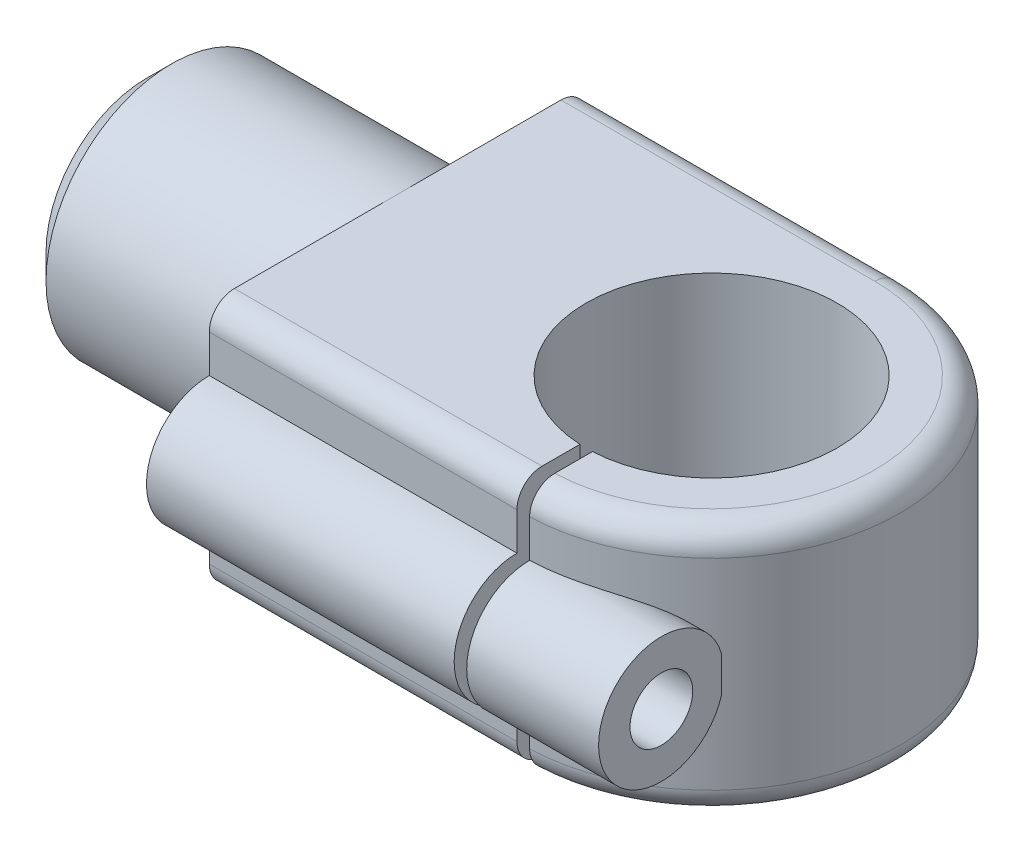
SolidWorks part; units mm, degrees
ref_plane "Front Plane" through (0, 0, 0) normal (0, 0, 1) x (1, 0, 0)
ref_plane "Top Plane" through (0, 0, 0) normal (0, 1, 0) x (1, 0, 0)
ref_plane "Right Plane" through (0, 0, 0) normal (1, 0, 0) x (0, 0, -1)
sketch "Sketch1" plane through (0, 0, 0) normal (0, 1, 0) x (1, 0, 0)
  line L0 (0, 15) -> (-30, 15)
  line L1 (-30, 15) -> (-30, -15)
  line L2 (-30, -15) -> (-0.5, -15)
  line L4 (0.5, -15) -> (0.5, -9.9875)
  line L5 (-0.5, -15) -> (-0.5, -9.9875)
  arc A0 (0.5, -9.9875) -> (-0.5, -9.9875) centre (0, 0) ccw
  arc A1 (0.5, -14.9917) -> (0, 15) centre (0, 0) ccw
  dimension "D1" = 20
  dimension "D2" = 30
  dimension "D3" = 30
extrude "Boss-Extrude1" add sketch "Sketch1" along normal blind 20 contours L4 A1 L0 L1 L2 L5 A0 region at (-12.0415, 0, -0.0669)
sketch "Sketch2" plane through (-30, 0, 0) normal (-1, 0, 0) x (0, 0, 1)
  line L0 (15, 20) -> (15, 0) construction
  circle A0 centre (15, 10) radius 5
  dimension "D1" = 10
extrude "Boss-Extrude2" add sketch "Sketch2" against normal blind 41
sketch "Sketch3" plane through (0, 20, 0) normal (0, 1, 0) x (1, 0, 0)
  line L0 (-0.5, -15) -> (-0.5, -9.9875) construction
  line L1 (0.5, -14.9917) -> (0.5, -9.9875) construction
  line L2 (-0.5, -15) -> (-0.5, -9.9875)
  line L3 (0.5, -14.9917) -> (0.5, -9.9875)
  line L4 (-0.5, -9.9875) -> (0.5, -9.9875)
  line L6 (-0.5, -15) -> (-0.5, -20)
  line L7 (-30, -20) -> (11, -20) construction
  line L8 (-0.5, -20) -> (0.5, -20)
  line L9 (0.5, -20) -> (0.5, -14.9917)
extrude "Cut-Extrude1" cut sketch "Sketch3" against normal blind 41
sketch "Sketch4" plane through (11, 0, 0) normal (1, 0, 0) x (0, 0, -1)
  circle A0 centre (-15, 10) radius 2.5
  dimension "D1" = 5
extrude "Cut-Extrude2" cut sketch "Sketch4" against normal blind 31
fillet "Fillet1" radius 2 6 edges at (-15, 0, -15) (-15, 20, -15) (-15.25, 20, 15) (-15.25, 0, 15) (14.9979, 0, -0.25) (14.9979, 20, -0.25)
sketch "Sketch5" plane through (-30, 0, 0) normal (-1, 0, 0) x (0, 0, 1)
  circle A0 centre (0, 10) radius 10
  dimension "D1" = 20
extrude "Boss-Extrude3" add sketch "Sketch5" along normal blind 15
sketch "Sketch6" plane through (-30, 0, 0) normal (-1, 0, 0) x (0, 0, 1)
  line L3 (0, 20) -> (-13, 20)
  line L4 (0, 0) -> (13, 0)
  line L5 (15, 2) -> (15, 5)
  line L6 (15, 15) -> (15, 18)
  line L7 (13, 20) -> (0, 20)
  line L8 (0, 0) -> (13, 0)
  line L9 (15, 2) -> (15, 5)
  line L10 (15, 15) -> (15, 18)
  line L11 (13, 20) -> (0, 20)
  line L12 (-15, 18) -> (-15, 2)
  line L13 (-13, 0) -> (0, 0)
  line L14 (0, 20) -> (-13, 20)
  line L15 (-15, 18) -> (-15, 2)
  line L16 (-13, 0) -> (0, 0)
  arc A3 (0, 20) -> (0, 0) centre (0, 10) ccw
  arc A4 (0, 0) -> (0, 20) centre (0, 10) ccw
  arc A5 (13, 0) -> (15, 2) centre (13, 2) ccw
  arc A6 (15, 5) -> (15, 15) centre (15, 10) ccw
  arc A7 (15, 18) -> (13, 20) centre (13, 18) ccw
  arc A8 (0, 0) -> (0, 20) centre (0, 10) ccw
  arc A9 (13, 0) -> (15, 2) centre (13, 2) ccw
  arc A10 (15, 5) -> (15, 15) centre (15, 10) ccw
  arc A11 (15, 18) -> (13, 20) centre (13, 18) ccw
  arc A12 (-13, 20) -> (-15, 18) centre (-13, 18) ccw
  arc A13 (-15, 2) -> (-13, 0) centre (-13, 2) ccw
  arc A14 (0, 20) -> (0, 0) centre (0, 10) ccw
  arc A15 (-13, 20) -> (-15, 18) centre (-13, 18) ccw
  arc A16 (-15, 2) -> (-13, 0) centre (-13, 2) ccw
  arc M15 (0, 20) -> (0, 0) centre (0, 10) cw
  line M16 (0, 0) -> (13, 0)
  arc M17 (13, 0) -> (15, 2) centre (13, 2) ccw
  line M18 (15, 2) -> (15, 5)
  arc M19 (15, 5) -> (15, 15) centre (15, 10) ccw
  line M20 (15, 15) -> (15, 18)
  arc M21 (15, 18) -> (13, 20) centre (13, 18) ccw
  line M22 (13, 20) -> (0, 20)
  dimension "D1" = 0
  dimension "D2" = 0
extrude "Cut-Extrude3" cut sketch "Sketch6" against normal blind 5 contours L15 A16 L16 A14 L14 A15 | M22 M15 M16 M17 M18 M19 M20 M21 region at (-30, 10, -11.0362) region at (-30, 10, 12.3604)
chamfer "Chamfer1" distance 2 angle 45 1 edges at (-45, 10, 10)
